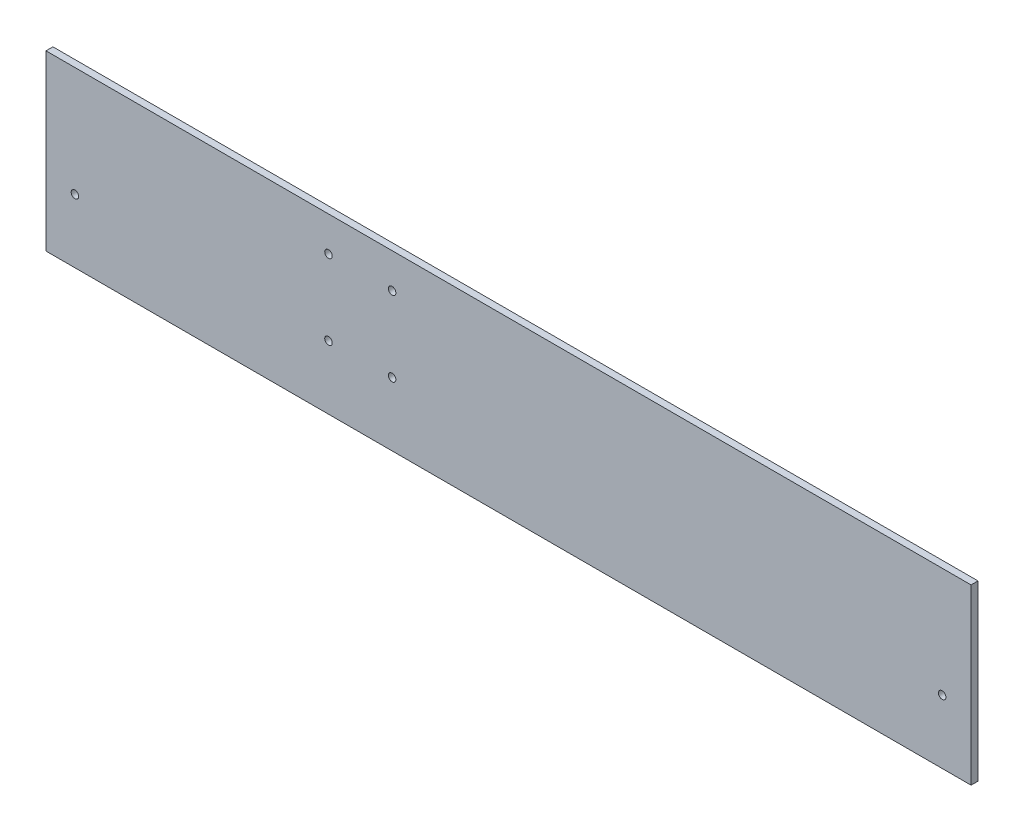
SolidWorks part; units mm, degrees
note: The reader was unsure of these and kept them because the rebuilt part matched: thickness of "Base-Flange1", "Sheet-Metal1", "Sheet-Metal2", "Sheet-Metal3".
ref_plane "Front Plane" through (0, 0, 0) normal (0, 0, 1) x (1, 0, 0)
ref_plane "Top Plane" through (0, 0, 0) normal (0, 1, 0) x (1, 0, 0)
ref_plane "Right Plane" through (0, 0, 0) normal (1, 0, 0) x (0, 0, -1)
sketch "Sketch1" plane through (0, 0, 0) normal (0, 0, 1) x (1, 0, 0)
  line L1 (-400, -75) -> (400, -75)
  line L2 (-400, -75) -> (-400, 75)
  line L3 (-400, 75) -> (400, 75)
  line L4 (400, -75) -> (400, 75)
  line L5 (-400, -75) -> (400, 75) construction
  line L6 (-400, 75) -> (400, -75) construction
  point P0 (0, 0)
  dimension "D1" = 150
  dimension "D2" = 800
base flange "Base-Flange1" sketch "Sketch1" thickness 6 reverse thickness direction no parameters "D1"=2
sketch "Sketch2" plane through (0, 0, 0) normal (0, 0, 1) x (1, 0, 0)
  line L0 (375, -20) -> (-375, -20) construction
  line L1 (0, 0) -> (0, -20) construction
  line L2 (400, 75) -> (-400, 75) construction
  line L3 (400, -75) -> (400, 75) construction
  circle A0 centre (-375, -20) radius 3.25
  circle A1 centre (375, -20) radius 3.25
  point P3 (0, -20)
  dimension "D3" = 6.5
  dimension "D1" = 95
  dimension "D2" = 25
extrude "Cut-Extrude1" cut sketch "Sketch2" against normal blind 10
sketch "Sketch3" plane through (0, 0, 0) normal (0, 0, 1) x (1, 0, 0)
  line L0 (400, 75) -> (-400, 75) construction
  line L1 (-155.7, -20) -> (-100.7, -20) construction
  line L2 (-155.7, -20) -> (-155.7, 45) construction
  line L3 (-155.7, 45) -> (-100.7, 45) construction
  line L4 (-100.7, -20) -> (-100.7, 45) construction
  line L5 (-155.7, -20) -> (-100.7, 45) construction
  line L6 (-155.7, 45) -> (-100.7, -20) construction
  line L7 (400, -75) -> (400, 75) construction
  circle A0 centre (-100.7, 45) radius 3.25
  circle A1 centre (-155.7, 45) radius 3.25
  circle A2 centre (-100.7, -20) radius 3.25
  circle A3 centre (-155.7, -20) radius 3.25
  point P0 (-128.2, 12.5)
  dimension "D5" = 6.5
  dimension "D1" = 55
  dimension "D2" = 65
  dimension "D3" = 30
  dimension "D4" = 500.7
extrude "Cut-Extrude2" cut sketch "Sketch3" against normal through all
sketch "Bend-Lines1" [suppressed] plane through (0, 0, 0) normal (0, 1, 0) x (1, 0, 0)
sketch "Bounding-Box1" [suppressed] plane through (0, 0, 0) normal (0, 1, 0) x (1, 0, 0)
sheet metal parameters "Sheet-Metal1" thickness 6 parameters "D1"=2, "D7"=1.5
flat pattern "Flat-Pattern1" [suppressed]
sketch "Bend-Lines2" plane through (0, 0, 0) normal (0, 1, 0) x (1, 0, 0)
sketch3d "Bounding-Box2" [suppressed]
  line L0 (-400, -75, 0) -> (400, -75, 0) construction
  line L1 (-400, 75, 0) -> (400, 75, 0) construction
  line L2 (-400, -75, 0) -> (-400, 75, 0) construction
  line L3 (400, -75, 0) -> (400, 75, 0) construction
sheet metal parameters "Sheet-Metal2" thickness 6 parameters "D1"=2, "D7"=1.5
flat pattern "Flat-Pattern1"
sketch "Bend-Lines2" plane through (0, 0, 0) normal (0, 1, 0) x (1, 0, 0)
sketch3d "Bounding-Box2" [suppressed]
  line L0 (-400, -75, 0) -> (400, -75, 0) construction
  line L1 (-400, 75, 0) -> (400, 75, 0) construction
  line L2 (-400, -75, 0) -> (-400, 75, 0) construction
  line L3 (400, -75, 0) -> (400, 75, 0) construction
sheet metal parameters "Sheet-Metal3" thickness 6 parameters "D1"=2, "D7"=1.5
flat pattern "Flat-Pattern1"
sketch "Bend-Lines2" plane through (0, 0, 0) normal (0, 1, 0) x (1, 0, 0)
sketch3d "Bounding-Box2" [suppressed]
  line L0 (-400, -75, 0) -> (400, -75, 0) construction
  line L1 (-400, 75, 0) -> (400, 75, 0) construction
  line L2 (-400, -75, 0) -> (-400, 75, 0) construction
  line L3 (400, -75, 0) -> (400, 75, 0) construction
